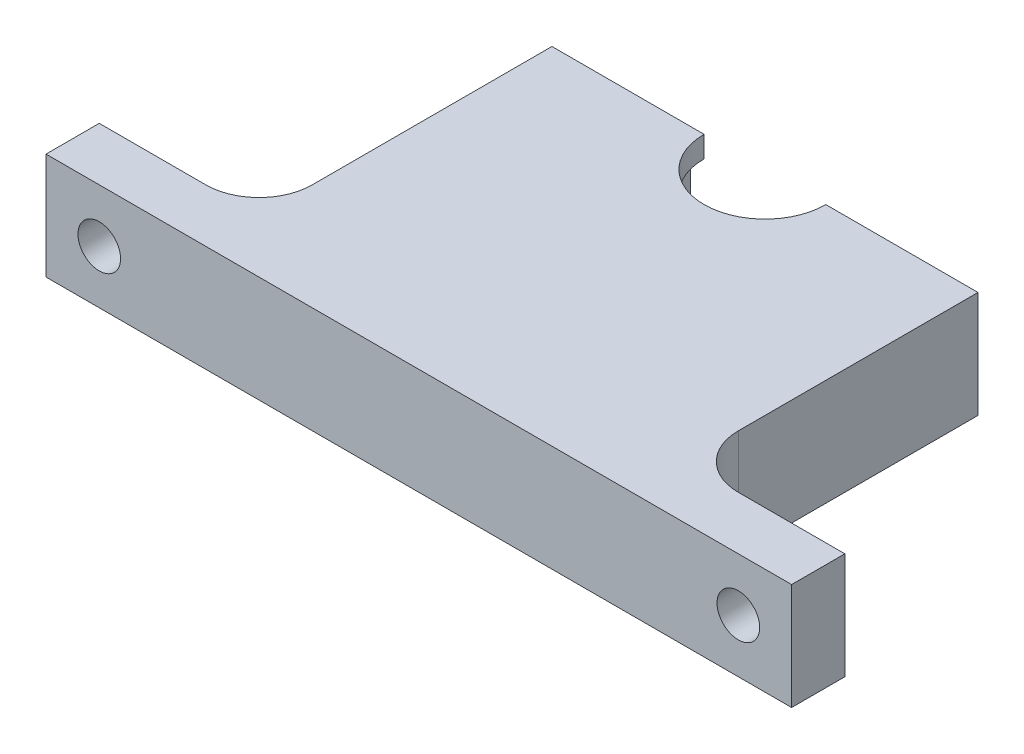
SolidWorks part; units mm, degrees
ref_plane "Front Plane" through (0, 0, 0) normal (0, 0, 1) x (1, 0, 0)
ref_plane "Top Plane" through (0, 0, 0) normal (0, 1, 0) x (1, 0, 0)
ref_plane "Right Plane" through (0, 0, 0) normal (1, 0, 0) x (0, 0, -1)
sketch "Sketch1" plane through (0, 0, 0) normal (0, 1, 0) x (1, 0, 0)
  line L0 (12.7, 0) -> (20, 0)
  line L1 (20, 0) -> (20, -32.5)
  line L2 (20, -32.5) -> (-20, -32.5)
  line L3 (-20, -32.5) -> (-20, 0)
  line L4 (-20, 0) -> (-12.7, 0)
  line L5 (-12.7, 0) -> (12.7, 0)
  circle A0 centre (0, 0) radius 5.715
  arc A1 (12.7, 0) -> (-12.7, 0) centre (0, 0) ccw
  point P8 (0, -32.5)
  dimension "D1" = 11.43
  dimension "D2" = 25.4
  dimension "D3" = 40
  dimension "D4" = 32.5
extrude "Boss-Extrude1" add sketch "Sketch1" along normal mid plane 10 contours A0 L5 L4 L3 L2 L1 L0 region at (0, 0, 16.818)
ref_plane "Plane1" through (0, 0, 0) normal (0, 1, 0) x (1, 0, 0)
sketch "Sketch3" plane through (0, 0, 0) normal (0, 1, 0) x (1, 0, 0)
  circle A0 centre (0, 0) radius 6.985
  dimension "D1" = 13.97
extrude "bearing cutout" cut sketch "Sketch3" against normal mid plane 6
sketch "Sketch4" plane through (0, 0, 0) normal (0, 0, -1) x (-1, 0, 0)
  line L0 (-20, 5) -> (-20, -5) construction
  line L1 (0, -5) -> (0, 5) construction
  line L2 (5.715, 5) -> (-5.715, 5) construction
  circle A0 centre (-15, 0) radius 1.5
  circle A2 centre (15, 0) radius 1.5
  point P5 (-20, 0)
  point P11 (0, 0)
  dimension "D1" = 3
  dimension "D2" = 5
extrude "top mount holes" cut sketch "Sketch4" against normal blind 10
sketch "Sketch6" plane through (0, 0, 32.5) normal (0, 0, 1) x (1, 0, 0)
  line L0 (20, 5) -> (-20, 5) construction
  line L1 (-35, 5) -> (-20, 5)
  line L2 (-35, 5) -> (-35, -5)
  line L3 (-35, -5) -> (-20, -5)
  line L4 (-20, 5) -> (-20, -5)
  line L5 (-35, 5) -> (-20, -5) construction
  line L6 (-35, -5) -> (-20, 5) construction
  line L7 (20, -5) -> (-20, -5) construction
  line L8 (-20, 5) -> (-20, -5) construction
  line L9 (0, -5) -> (0, 5) construction
  line L10 (35, -5) -> (20, -5)
  line L11 (20, 5) -> (20, -5)
  line L12 (35, 5) -> (20, 5)
  line L13 (35, 5) -> (35, -5)
  line L14 (-35, 0) -> (-20, 0) construction
  circle A0 centre (-30, 0) radius 2
  circle A1 centre (30, 0) radius 2
  point P0 (-27.5, 0)
  point P17 (0, 0)
  point P24 (-31.0428, 0)
  point P28 (-27.5, 0)
  dimension "D2" = 4
  dimension "D1" = 15
  dimension "D3" = 5
extrude "mounting holes" add sketch "Sketch6" against normal blind 5
fillet "Fillet1" radius 5 2 edges at (20, 0, 27.5) (-20, 0, 27.5)
